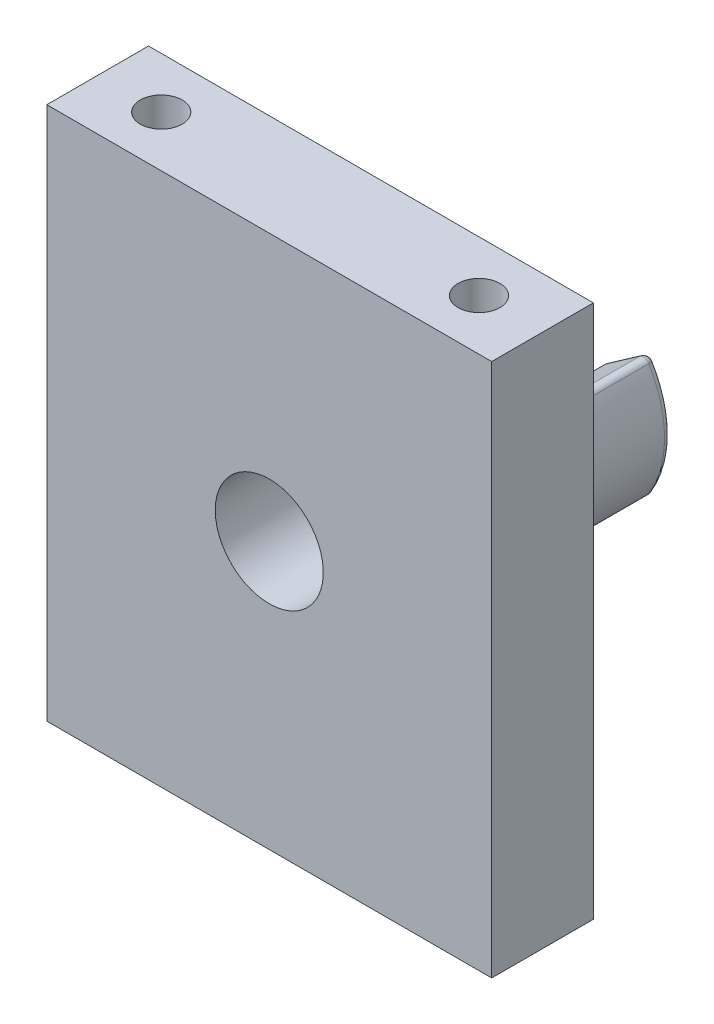
SolidWorks part; units mm, degrees
material "6061 合金"
ref_plane "前视基准面" through (0, 0, 0) normal (0, 0, 1) x (1, 0, 0)
ref_plane "上视基准面" through (0, 0, 0) normal (0, 1, 0) x (1, 0, 0)
ref_plane "右视基准面" through (0, 0, 0) normal (1, 0, 0) x (0, 0, -1)
sketch "草图1" plane through (0, 0, 0) normal (0, 0, 1) x (1, 0, 0)
  line L1 (-17.5, 21) -> (17.5, 21)
  line L2 (-17.5, 21) -> (-17.5, -21)
  line L3 (-17.5, -21) -> (17.5, -21)
  line L4 (17.5, 21) -> (17.5, -21)
  line L5 (-17.5, 21) -> (17.5, -21) construction
  line L6 (-17.5, -21) -> (17.5, 21) construction
  point P0 (0, 0)
  dimension "D1" = 35
  dimension "D2" = 42
extrude "凸台-拉伸1" add sketch "草图1" along normal mid plane 8
sketch "草图2" plane through (0, 21, 0) normal (0, 1, 0) x (1, 0, 0)
  line L0 (-12.5, 0) -> (12.5, 0) construction
  point P3 (0, 0)
  dimension "D1" = 25
hole_wizard "M4 螺纹孔1" positions "草图3" profile "草图4" tap size "M4" standard "ISO" end condition through all
sketch "草图3" plane through (0, 21, 0) normal (0, 1, 0) x (1, 0, 0)
  point P0 (-12.5, 0)
  point P3 (12.5, 0)
sketch "草图4" plane through (-12.5, 21, 0) normal (1, 0, 0) x (0, 0, 1)
  line L0 (0, 0) -> (0, 42)
  line L1 (0, 42) -> (1.65, 42)
  line L2 (1.65, 42) -> (1.65, 0)
  line L5 (1.65, 0) -> (0, 0)
  line L11 (0, -6.35) -> (0, 107.95) construction
  dimension "通孔螺纹孔钻头直径" = 3.3
  dimension "通孔螺纹孔钻头深度" = 42
cosmetic thread "孔螺蚊线1" parameters "D2"=4
cosmetic thread "孔螺蚊线2" parameters "D2"=4
sketch "草图5" plane through (0, 0, -4) normal (0, 0, -1) x (-1, 0, 0)
  circle A0 centre (0, 0) radius 8.5
  dimension "D1" = 17
extrude "凸台-拉伸2" add sketch "草图5" along normal blind 10.1
sketch "草图6" plane through (0, 0, 0) normal (0, 1, 0) x (1, 0, 0)
  line L0 (8.5, 4) -> (8.5, 14.1) construction
  line L1 (8.5, 10) -> (10, 10)
  line L2 (8.5, 10) -> (8.5, 4)
  line L3 (8.5, 4) -> (10, 4)
  line L4 (10, 10) -> (10, 4)
  line L5 (17.5, 4) -> (-17.5, 4) construction
  line L6 (0, 0) -> (0, 4) construction
  dimension "D1" = 6
  dimension "D3" = 10
revolve "旋转1" add sketch "草图6" angle 360 about L6
chamfer "倒角1" distance 0.5 angle 45 1 edges at (10, 0, -10)
sketch "草图7" plane through (0, 0, -14.1) normal (0, 0, -1) x (-1, 0, 0)
  circle A0 centre (0, 0) radius 6.5 construction
  dimension "D1" = 13
hole_wizard "M3 螺纹孔1" positions "草图8" profile "草图9" tap size "M3" standard "ISO"
sketch "草图8" plane through (0, 0, -14.1) normal (0, 0, -1) x (-1, 0, 0)
  circle A0 centre (0, 0) radius 6.5 construction
  point P0 (0, 6.5)
  point P6 (0, -6.5)
sketch "草图9" plane through (0, 6.5, -14.1) normal (1, 0, 0) x (0, 1, 0)
  line L0 (0, 0) -> (0, 10.7511)
  line L1 (0, 10.7511) -> (1.25, 10)
  line L2 (1.25, 10) -> (1.25, 0)
  line L5 (1.25, 0) -> (0, 0)
  line L10 (0, 10.7511) -> (-1.25, 10) construction
  line L11 (0, -6.35) -> (0, 107.95) construction
  dimension "螺纹孔钻头直径" = 2.5
  dimension "螺纹孔钻头深度" = 10
  dimension "导头角度" = 118
cosmetic thread "孔螺蚊线4" parameters "D1"=6, "D2"=3
cosmetic thread "孔螺蚊线6" parameters "D1"=6, "D2"=3
sketch "草图10" plane through (0, 0, -14.1) normal (0, 0, -1) x (-1, 0, 0)
  circle A0 centre (0, 0) radius 4.25
  dimension "D1" = 8.5
extrude "切除-拉伸1" cut sketch "草图10" against normal through all
sketch "草图12" plane through (0, 0, -4) normal (0, 0, -1) x (-1, 0, 0)
  line L0 (17.5, 0) -> (21, 0)
  line L1 (-17.5, 21) -> (17.5, 21)
  line L2 (-17.5, 21) -> (-17.5, -21)
  line L3 (-17.5, -21) -> (17.5, -21)
  line L4 (17.5, 21) -> (17.5, -21)
  line L5 (-17.5, 21) -> (17.5, -21) construction
  line L6 (-17.5, -21) -> (17.5, 21) construction
  line L7 (-17.5, 0) -> (-21, 0)
  line L8 (-17.5, 11.6082) -> (-13.0958, 11.6082)
  line L9 (13.0958, 11.6082) -> (17.5, 11.6082)
  line L10 (17.5, -11.6082) -> (13.0958, -11.6082)
  line L11 (-13.0958, -11.6082) -> (-17.5, -11.6082)
  circle A0 centre (0, 0) radius 17.5
  circle A1 centre (0, 0) radius 21
  dimension "D1" = 42
  dimension "D2" = 35
sketch "草图13" plane through (0, 0, -14.1) normal (0, 0, -1) x (-1, 0, 0)
  line L0 (-8.5, 0) -> (8.5, 0) construction
  line L1 (6.9628, 4.8754) -> (0, 0)
  line L2 (0, 0) -> (6.9628, -4.8754)
  circle A0 centre (0, 0) radius 4.25
  circle A1 centre (0, 0) radius 8.5
  circle A3 centre (0, 0) radius 8.5 construction
  circle M6 centre (0, 0) radius 4.25
  circle M9 centre (0, 0) radius 8.5
  dimension "D1" = 8.5
  dimension "D2" = 35
  dimension "D3" = 35
extrude "凸台-拉伸3" add sketch "草图13" along normal blind 5 contours L0 A1 L1 M6 | L0 A0 L2 M9 region at (-6.2076, 1.9572, -14.1) region at (-6.2076, -1.9572, -14.1)
mirror "镜向1" about plane through (0, 0, 0) normal (1, 0, 0) of "凸台-拉伸3"
fillet "圆角1" radius 0.5 16 edges at (-5.2221, 3.6565, -19.1) (-5.2221, -3.6565, -19.1) (-4.25, 0, -19.1) (-8.5, 0, -19.1) (5.2221, -3.6565, -19.1) (5.2221, 3.6565, -19.1) (8.5, 0, -19.1) (4.25, 0, -19.1) (3.4814, 2.4377, -16.6) (6.9628, 4.8754, -16.6) (6.9628, -4.8754, -16.6) (3.4814, -2.4377, -16.6) (-3.4814, 2.4377, -16.6) (-6.9628, 4.8754, -16.6) (-6.9628, -4.8754, -16.6) (-3.4814, -2.4377, -16.6)
